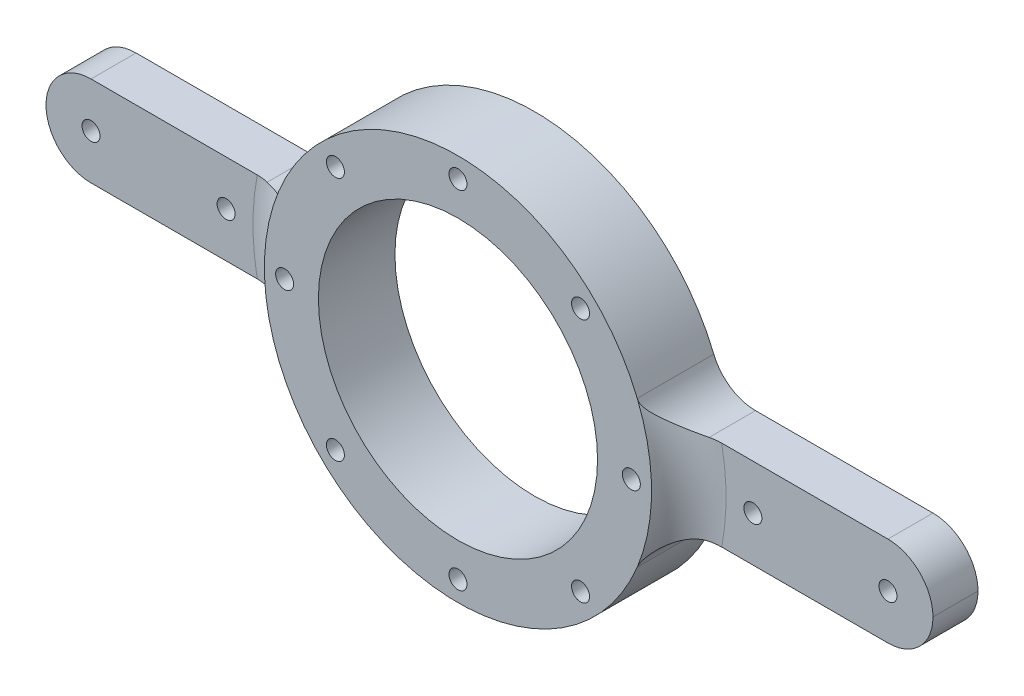
SolidWorks part; units mm, degrees
ref_plane "Front Plane" through (0, 0, 0) normal (0, 0, 1) x (1, 0, 0)
ref_plane "Top Plane" through (0, 0, 0) normal (0, 1, 0) x (1, 0, 0)
ref_plane "Right Plane" through (0, 0, 0) normal (1, 0, 0) x (0, 0, -1)
sketch "Sketch1" plane through (0, 0, 0) normal (0, 0, 1) x (1, 0, 0)
  line L0 (98.5, 0) -> (18.5, 0) construction
  line L1 (-41.821, 10) -> (-98.5, 10)
  line L2 (-98.5, 10) -> (-98.5, -10)
  line L3 (-98.5, -10) -> (-41.821, -10)
  line L4 (41.821, 10) -> (98.5, 10)
  line L5 (98.5, 10) -> (98.5, -10)
  line L6 (98.5, -10) -> (41.821, -10)
  line L7 (-43, 0) -> (-98.5, 0) construction
  circle A0 centre (0, 0) radius 31
  arc A1 (41.821, 10) -> (-41.821, 10) centre (0, 0) ccw
  arc A2 (-41.821, -10) -> (41.821, -10) centre (0, 0) ccw
  circle A3 centre (0, 38.5) radius 2
  circle A4 centre (27.2236, 27.2236) radius 2
  circle A5 centre (38.5, 0) radius 2
  circle A6 centre (27.2236, -27.2236) radius 2
  circle A7 centre (0, -38.5) radius 2
  circle A8 centre (-27.2236, -27.2236) radius 2
  circle A9 centre (-38.5, 0) radius 2
  circle A10 centre (-27.2236, 27.2236) radius 2
  circle A11 centre (-58.5, 0) radius 2
  circle A12 centre (-88.5, 0) radius 2
  circle A13 centre (58.5, 0) radius 2
  circle A14 centre (88.5, 0) radius 2
  arc A15 (-41.821, 10) -> (-41.7932, -10.1156) centre (0, 0) ccw
  arc A16 (41.821, 10) -> (41.7317, -10.3665) centre (0, 0) cw
  point P7 (0, 0)
  point P19 (-98.5, 0)
  point P35 (0, 0)
  dimension "D1" = 4
  dimension "D3" = 62
  dimension "D4" = 43
  dimension "D7" = 4
  dimension "D2" = 38.5
  dimension "D6" = 20
  dimension "D8" = 20
  dimension "D9" = 30
  dimension "D10" = 20
  dimension "D11" = 30
  dimension "D12" = 10
  dimension "D13" = 10
  dimension "D5" = 8
extrude "Boss-Extrude1" add sketch "Sketch1" along normal blind 17 contours A16 A1 A15 A2 A0 A3 A4 A5 A6 A7 A8 A9 A10 region at (0, 41.7838, 0)
extrude "Boss-Extrude2" add sketch "Sketch1<3>" along normal blind 10 contours A15 L1 L2 L3 A12 A11 | L4 A16 L6 L5 A14 A13 region at (-70.4857, 0, 0) region at (70.4857, 0, 0)
sketch "Sketch1<3>" plane through (0, 0, 0) normal (0, 0, 1) x (1, 0, 0) same geometry as "Sketch1"
fillet "Fillet1" radius 10 6 edges at (-41.821, 10, 5) (-41.821, -10, 5) (41.821, 10, 5) (41.821, -10, 5) (43, 0, 10) (-43, 0, 10)
fillet "Fillet2" radius 10 4 edges at (98.5, -10, 5) (98.5, 10, 5) (-98.5, -10, 5) (-98.5, 10, 5)
